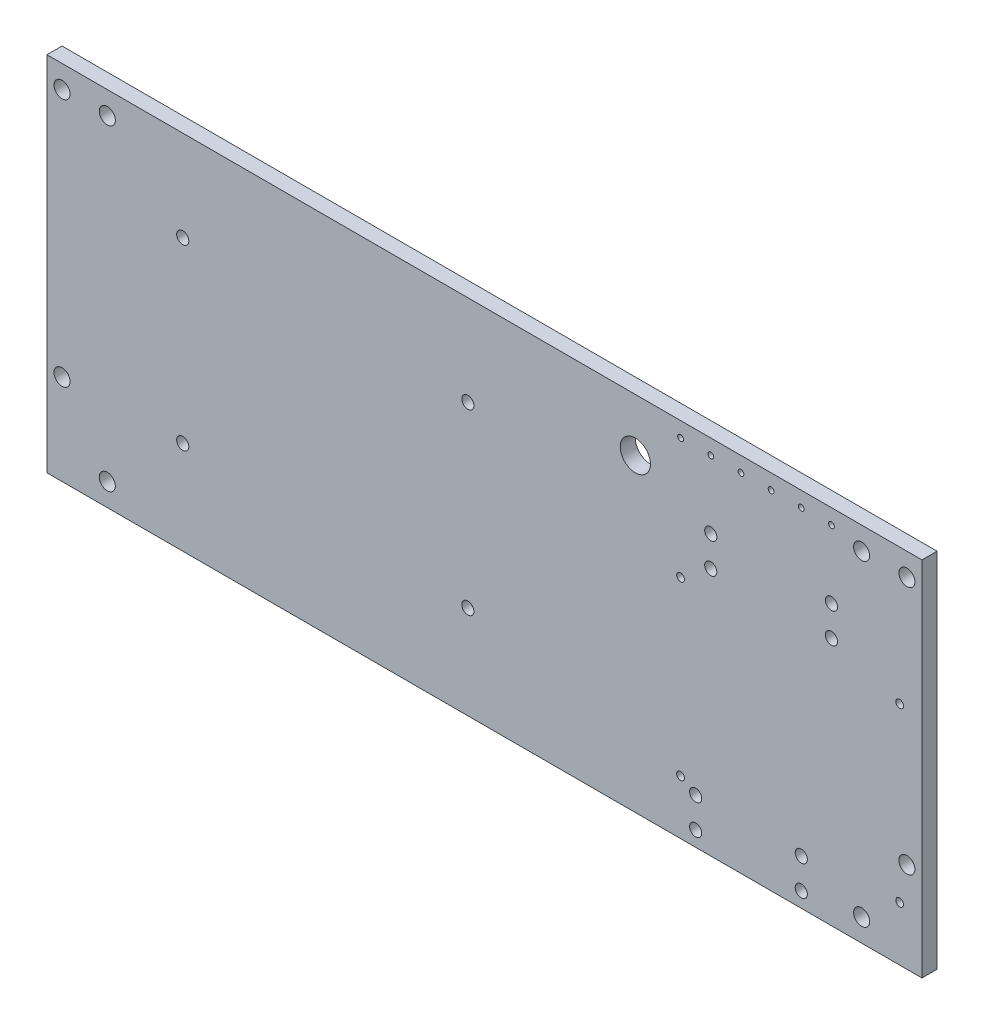
SolidWorks part; units mm, degrees
material "6061 Alloy"
ref_plane "Front Plane" through (0, 0, 0) normal (0, 0, 1) x (1, 0, 0)
ref_plane "Top Plane" through (0, 0, 0) normal (0, 1, 0) x (1, 0, 0)
ref_plane "Right Plane" through (0, 0, 0) normal (1, 0, 0) x (0, 0, -1)
sketch "Sketch1" plane through (0, 0, 0) normal (0, 0, 1) x (1, 0, 0)
  line L1 (-184.15, 76.2) -> (184.15, 76.2)
  line L2 (-184.15, 76.2) -> (-184.15, -76.2)
  line L3 (-184.15, -76.2) -> (184.15, -76.2)
  line L4 (184.15, 76.2) -> (184.15, -76.2)
  line L5 (-184.15, 76.2) -> (184.15, -76.2) construction
  line L6 (-184.15, -76.2) -> (184.15, 76.2) construction
  point P0 (0, 0)
  dimension "D1" = 152.4
  dimension "D2" = 368.3
extrude "Boss-Extrude1" add sketch "Sketch1" along normal blind 6.35
hole_wizard "#4 Clearance Hole1" positions "Sketch4" profile "Sketch5" hole size "#4" standard "ANSI Inch" end condition up to next
sketch "Sketch4" plane through (0, 0, 0) normal (0, 0, -1) x (-1, 0, 0)
  line L1 (-174.752, 19.05) -> (-82.55, 19.05) construction
  line L2 (-174.752, 19.05) -> (-174.752, -53.34) construction
  line L3 (-174.752, -53.34) -> (-82.55, -53.34) construction
  line L4 (-82.55, 19.05) -> (-82.55, -53.34) construction
  line L7 (-184.15, -76.2) -> (-184.15, 76.2) construction
  line L8 (-184.15, 76.2) -> (184.15, 76.2) construction
  point P1 (-174.752, 19.05)
  point P2 (-82.55, -53.34)
  point P169 (-174.752, -53.34)
  point P170 (-82.55, 19.05)
  dimension "D1" = 92.202
  dimension "D2" = 72.39
  dimension "D3" = 9.398
  dimension "D4" = 57.15
sketch "Sketch5" plane through (174.752, 19.05, 0) normal (1, 0, 0) x (0, 1, 0)
  line L0 (0, 0) -> (0, 6.35)
  line L1 (0, 6.35) -> (1.6319, 6.35)
  line L2 (1.6319, 6.35) -> (1.6319, 0)
  line L5 (1.6319, 0) -> (0, 0)
  line L11 (0, -6.35) -> (0, 107.95) construction
  dimension "Thru Hole Dia." = 3.2639
  dimension "Thru Hole Depth" = 6.35
hole_wizard "1/4 Clearance Hole1" positions "Sketch7" profile "Sketch6" hole size "1/4" standard "ANSI Inch" end condition up to next
sketch "Sketch7" plane through (0, 0, 0) normal (0, 0, -1) x (-1, 0, 0)
  line L1 (-158.75, 66.675) -> (158.75, 66.675) construction
  line L2 (-158.75, 66.675) -> (-158.75, -66.675) construction
  line L3 (-158.75, -66.675) -> (158.75, -66.675) construction
  line L4 (158.75, 66.675) -> (158.75, -66.675) construction
  line L5 (-158.75, 0) -> (158.75, 0) construction
  line L7 (-184.15, 76.2) -> (184.15, 76.2) construction
  line L8 (-184.15, -76.2) -> (-184.15, 76.2) construction
  point P0 (-158.75, 66.675)
  point P1 (158.75, -66.675)
  point P222 (-158.75, -66.675)
  point P223 (158.75, 66.675)
  dimension "D1" = 9.525
  dimension "D2" = 25.4
sketch "Sketch6" plane through (158.75, 66.675, 0) normal (1, 0, 0) x (0, 1, 0)
  line L0 (0, 0) -> (0, 6.35)
  line L1 (0, 6.35) -> (3.3782, 6.35)
  line L2 (3.3782, 6.35) -> (3.3782, 0)
  line L5 (3.3782, 0) -> (0, 0)
  line L11 (0, -6.35) -> (0, 107.95) construction
  dimension "Thru Hole Dia." = 6.7564
  dimension "Thru Hole Depth" = 6.35
hole_wizard "1/4 Clearance Hole2" positions "Sketch9" profile "Sketch8" hole size "1/4" standard "ANSI Inch" end condition up to next
sketch "Sketch9" plane through (0, 0, 0) normal (0, 0, -1) x (-1, 0, 0)
  line L1 (-177.8, 66.675) -> (177.8, 66.675) construction
  line L2 (-177.8, 66.675) -> (-177.8, -38.1) construction
  line L3 (-177.8, -38.1) -> (177.8, -38.1) construction
  line L4 (177.8, 66.675) -> (177.8, -38.1) construction
  line L7 (-184.15, -76.2) -> (-184.15, 76.2) construction
  line L8 (-184.15, 76.2) -> (184.15, 76.2) construction
  line L9 (184.15, -76.2) -> (-184.15, -76.2) construction
  line L10 (184.15, 76.2) -> (184.15, -76.2) construction
  point P0 (-177.8, 66.675)
  point P1 (177.8, -38.1)
  point P222 (-177.8, -38.1)
  point P223 (177.8, 66.675)
  dimension "D1" = 6.35
  dimension "D2" = 9.525
  dimension "D3" = 38.1
  dimension "D4" = 6.35
sketch "Sketch8" plane through (177.8, 66.675, 0) normal (1, 0, 0) x (0, 1, 0)
  line L0 (0, 0) -> (0, 6.35)
  line L1 (0, 6.35) -> (3.3782, 6.35)
  line L2 (3.3782, 6.35) -> (3.3782, 0)
  line L5 (3.3782, 0) -> (0, 0)
  line L11 (0, -6.35) -> (0, 107.95) construction
  dimension "Thru Hole Dia." = 6.7564
  dimension "Thru Hole Depth" = 6.35
sketch "Sketch10" plane through (0, 0, 0) normal (0, 0, -1) x (-1, 0, 0)
  line L0 (-184.15, 76.2) -> (184.15, 76.2) construction
  line L1 (-184.15, -76.2) -> (-184.15, 76.2) construction
  circle A0 centre (-63.5, 53.975) radius 6.35
  dimension "D2" = 22.225
  dimension "D1" = 12.7
  dimension "D3" = 120.65
extrude "Cut-Extrude1" cut sketch "Sketch10" against normal through all
hole_wizard "#2 Clearance Hole1" positions "Sketch12" profile "Sketch11" hole size "#2" standard "ANSI Inch" end condition up to next
sketch "Sketch12" plane through (0, 0, 0) normal (0, 0, -1) x (-1, 0, 0)
  line L0 (-133.35, 69.85) -> (-146.05, 69.85) construction
  line L3 (-184.15, 76.2) -> (184.15, 76.2) construction
  line L4 (-184.15, -76.2) -> (-184.15, 76.2) construction
  line L5 (-120.65, 69.85) -> (-107.95, 69.85) construction
  line L7 (-95.25, 69.85) -> (-82.55, 69.85) construction
  point P1 (-133.35, 69.85)
  point P2 (-146.05, 69.85)
  point P27 (-120.65, 69.85)
  point P28 (-107.95, 69.85)
  point P31 (-95.25, 69.85)
  point P32 (-82.55, 69.85)
  dimension "D1" = 12.7
  dimension "D2" = 6.35
  dimension "D3" = 38.1
  dimension "D4" = 12.7
  dimension "D5" = 12.7
sketch "Sketch11" plane through (133.35, 69.85, 0) normal (1, 0, 0) x (0, 1, 0)
  line L0 (0, 0) -> (0, 6.35)
  line L1 (0, 6.35) -> (1.2192, 6.35)
  line L2 (1.2192, 6.35) -> (1.2192, 0)
  line L5 (1.2192, 0) -> (0, 0)
  line L11 (0, -6.35) -> (0, 107.95) construction
  dimension "Thru Hole Dia." = 2.4384
  dimension "Thru Hole Depth" = 6.35
hole_wizard "#10 Clearance Hole2" positions "Sketch14" profile "Sketch13" hole size "#10" standard "ANSI Inch" end condition up to next
sketch "Sketch14" plane through (0, 0, 0) normal (0, 0, -1) x (-1, 0, 0)
  line L0 (-146.05, 41.275) -> (-146.05, 28.575) construction
  line L4 (-95.25, 41.275) -> (-95.25, 28.575) construction
  line L5 (-184.15, 76.2) -> (184.15, 76.2) construction
  line L6 (-184.15, -76.2) -> (-184.15, 76.2) construction
  point P1 (-146.05, 41.275)
  point P2 (-146.05, 28.575)
  point P9 (-95.25, 41.275)
  point P10 (-95.25, 28.575)
  dimension "D1" = 12.7
  dimension "D2" = 34.925
  dimension "D3" = 38.1
  dimension "D4" = 50.8
sketch "Sketch13" plane through (146.05, 41.275, 0) normal (1, 0, 0) x (0, 1, 0)
  line L0 (0, 0) -> (0, 6.35)
  line L1 (0, 6.35) -> (2.5527, 6.35)
  line L2 (2.5527, 6.35) -> (2.5527, 0)
  line L5 (2.5527, 0) -> (0, 0)
  line L11 (0, -6.35) -> (0, 107.95) construction
  dimension "Thru Hole Dia." = 5.1054
  dimension "Thru Hole Depth" = 6.35
hole_wizard "#10 Clearance Hole1" positions "Sketch16" profile "Sketch17" hole size "#10" standard "ANSI Inch" end condition up to next
sketch "Sketch16" plane through (0, 0, 0) normal (0, 0, -1) x (-1, 0, 0)
  line L1 (7, 38.1) -> (127, 38.1) construction
  line L2 (7, 38.1) -> (7, -36.9) construction
  line L3 (7, -36.9) -> (127, -36.9) construction
  line L4 (127, 38.1) -> (127, -36.9) construction
  line L5 (184.15, 76.2) -> (184.15, -76.2) construction
  line L6 (-184.15, 76.2) -> (184.15, 76.2) construction
  point P0 (7, 38.1)
  point P1 (127, -36.9)
  point P78 (7, -36.9)
  point P79 (127, 38.1)
  dimension "D1" = 57.15
  dimension "D2" = 38.1
  dimension "D3" = 120
  dimension "D4" = 75
sketch "Sketch17" plane through (-7, 38.1, 0) normal (1, 0, 0) x (0, 1, 0)
  line L0 (0, 0) -> (0, 6.35)
  line L1 (0, 6.35) -> (2.5527, 6.35)
  line L2 (2.5527, 6.35) -> (2.5527, 0)
  line L5 (2.5527, 0) -> (0, 0)
  line L11 (0, -6.35) -> (0, 107.95) construction
  dimension "Thru Hole Dia." = 5.1054
  dimension "Thru Hole Depth" = 6.35
hole_wizard "#10 Clearance Hole3" positions "Sketch20" profile "Sketch21" hole size "#10" standard "ANSI Inch" end condition up to next
sketch "Sketch20" plane through (0, 0, 0) normal (0, 0, -1) x (-1, 0, 0)
  line L1 (-133.35, -57.15) -> (-88.9, -57.15) construction
  line L2 (-133.35, -57.15) -> (-133.35, -69.85) construction
  line L3 (-133.35, -69.85) -> (-88.9, -69.85) construction
  line L4 (-88.9, -57.15) -> (-88.9, -69.85) construction
  line L5 (184.15, -76.2) -> (-184.15, -76.2) construction
  line L6 (-184.15, -76.2) -> (-184.15, 76.2) construction
  point P1 (-133.35, -57.15)
  point P2 (-88.9, -69.85)
  point P205 (-133.35, -69.85)
  point P206 (-88.9, -57.15)
  dimension "D1" = 12.7
  dimension "D2" = 44.45
  dimension "D3" = 6.35
  dimension "D4" = 50.8
sketch "Sketch21" plane through (133.35, -57.15, 0) normal (1, 0, 0) x (0, 1, 0)
  line L0 (0, 0) -> (0, 6.35)
  line L1 (0, 6.35) -> (2.5527, 6.35)
  line L2 (2.5527, 6.35) -> (2.5527, 0)
  line L5 (2.5527, 0) -> (0, 0)
  line L11 (0, -6.35) -> (0, 107.95) construction
  dimension "Thru Hole Dia." = 5.1054
  dimension "Thru Hole Depth" = 6.35
